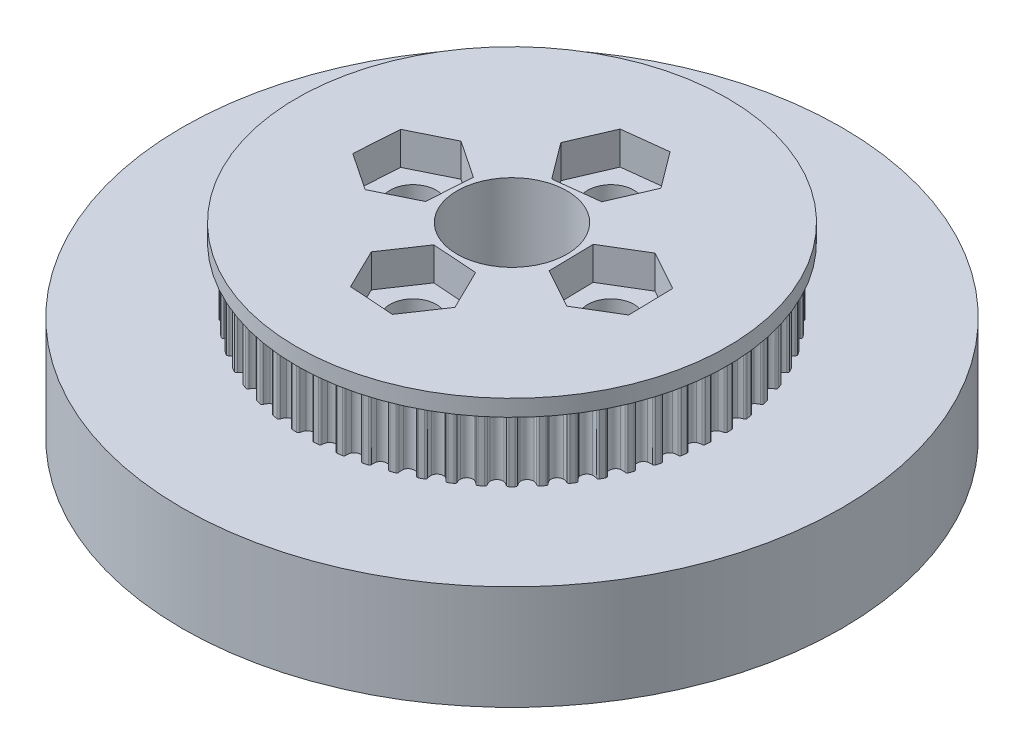
SolidWorks part; units mm, degrees
ref_plane "Front Plane" through (0, 0, 0) normal (0, 0, 1) x (1, 0, 0)
ref_plane "Top Plane" through (0, 0, 0) normal (0, 1, 0) x (1, 0, 0)
ref_plane "Right Plane" through (0, 0, 0) normal (1, 0, 0) x (0, 0, -1)
sketch "Sketch1" plane through (0, 0, 0) normal (0, 1, 0) x (1, 0, 0)
  circle A0 centre (0, 0) radius 18.8446
  dimension "D1" = 37.6892
extrude "Boss-Extrude1" add sketch "Sketch1" along normal blind 6
sketch "Sketch2" plane through (0, 6, 0) normal (0, 1, 0) x (1, 0, 0)
  line L0 (0, 0) -> (0, 18.8446) construction
  line L1 (0, 18.8446) -> (-0.4, 18.8446) construction
  line L2 (0, 18.8446) -> (0.4, 18.8446) construction
  circle A0 centre (0, 0) radius 18.8446
  circle A1 centre (0, 0) radius 18.6396 construction
  circle A2 centre (0, 0) radius 18.0846 construction
  arc A4 (-0.6199, 18.8344) -> (-0.4536, 18.2862) centre (0.4, 18.8446) ccw
  arc A5 (-0.4536, 18.2862) -> (0.4536, 18.2862) centre (0, 18.6396) ccw
  arc A6 (0.4536, 18.2862) -> (0.6199, 18.8344) centre (-0.4, 18.8446) ccw
  dimension "D1" = 37.6892
  dimension "D2" = 36.1692
  dimension "D3" = 37.2792
  dimension "D7" = 2.04
  dimension "D8" = 1.15
  dimension "D4" = 0.4
  dimension "D5" = 0.4
extrude "Cut-Extrude1" cut sketch "Sketch2" against normal blind 10 contours A5 A6 A0 A4 region at (0, 6, -18.5075)
fillet "Fillet1" radius 0.17 2 edges at (0.6199, 3, -18.8344) (-0.6199, 3, -18.8344)
ref_axis "Axis2" through (0, 6, 0) along (0, -1, 0)
pattern_circular "CirPattern2" count 60 over 360 about axis through (0, 6, 0) along (0, -1, 0) of "Cut-Extrude1", "Fillet1"
sketch "Sketch3" plane through (0, 6, 0) normal (0, 1, 0) x (1, 0, 0)
  circle A0 centre (0, 0) radius 19.5946
  dimension "D1" = 39.1892
extrude "Boss-Extrude2" add sketch "Sketch3" along normal blind 1.5
sketch "Sketch4" plane through (0, 0, 0) normal (0, -1, 0) x (1, 0, 0)
  circle A0 centre (0, 0) radius 30
  dimension "D1" = 60
extrude "Boss-Extrude3" add sketch "Sketch4" along normal blind 9.5
sketch "Sketch5" plane through (0, -9.5, 0) normal (0, -1, 0) x (1, 0, 0)
  circle A0 centre (0, 0) radius 24.5
  dimension "D1" = 49
extrude "Cut-Extrude2" cut sketch "Sketch5" against normal blind 4
sketch "Sketch6" plane through (0, -5.5, 0) normal (0, -1, 0) x (1, 0, 0)
  circle A0 centre (0, 0) radius 17
  dimension "D1" = 34
extrude "Boss-Extrude4" add sketch "Sketch6" along normal blind 2
sketch "Sketch7" plane through (0, -7.5, 0) normal (0, -1, 0) x (1, 0, 0)
  circle A0 centre (0, 0) radius 12.25
  dimension "D1" = 24.5
extrude "Boss-Extrude5" add sketch "Sketch7" along normal blind 13
sketch "Sketch8" plane through (0, -20.5, 0) normal (0, -1, 0) x (1, 0, 0)
  circle A0 centre (0, 0) radius 9 construction
  circle A1 centre (0, 9) radius 2.1
  circle A2 centre (9, 0) radius 2.1
  circle A3 centre (0, -9) radius 2.1
  circle A4 centre (-9, 0) radius 2.1
  dimension "D1" = 4.2
  dimension "D2" = 18
extrude "Cut-Extrude3" cut sketch "Sketch8" against normal through all
sketch "Sketch9" plane through (0, 7.5, 0) normal (0, 1, 0) x (1, 0, 0)
  line L31 (5.4102, 1.979) -> (5.4912, -2.1194)
  line L32 (5.4912, -2.1194) -> (9.0811, -4.0984)
  line L33 (9.0811, -4.0984) -> (12.5898, -1.979)
  line L34 (12.5898, -1.979) -> (12.5088, 2.1194)
  line L35 (12.5088, 2.1194) -> (8.9189, 4.0984)
  line L36 (8.9189, 4.0984) -> (5.4102, 1.979)
  line L37 (-4.0711, 8.5212) -> (-1.6209, 5.2349)
  line L38 (-1.6209, 5.2349) -> (2.4502, 5.7137)
  line L39 (2.4502, 5.7137) -> (4.0711, 9.4788)
  line L40 (4.0711, 9.4788) -> (1.6209, 12.7651)
  line L41 (1.6209, 12.7651) -> (-2.4502, 12.2863)
  line L42 (-2.4502, 12.2863) -> (-4.0711, 8.5212)
  line L43 (-5.3231, 1.8122) -> (-8.731, 4.0903)
  line L44 (-8.731, 4.0903) -> (-12.4078, 2.2782)
  line L45 (-12.4078, 2.2782) -> (-12.6769, -1.8122)
  line L46 (-12.6769, -1.8122) -> (-9.269, -4.0903)
  line L47 (-9.269, -4.0903) -> (-5.5922, -2.2782)
  line L48 (-5.5922, -2.2782) -> (-5.3231, 1.8122)
  line L49 (-1.7979, -5.3161) -> (-4.0893, -8.7151)
  line L50 (-4.0893, -8.7151) -> (-2.2914, -12.399)
  line L51 (-2.2914, -12.399) -> (1.7979, -12.6839)
  line L52 (1.7979, -12.6839) -> (4.0893, -9.2849)
  line L53 (4.0893, -9.2849) -> (2.2914, -5.601)
  line L54 (2.2914, -5.601) -> (-1.7979, -5.3161)
  circle A0 centre (9, 0) radius 3.55 construction
  circle A1 centre (0, 9) radius 3.55 construction
  circle A2 centre (-9, 0) radius 3.55 construction
  circle A3 centre (0, -9) radius 3.55 construction
  dimension "D1" = 7.1
  dimension "D2" = 7.1
  dimension "D3" = 7.1
  dimension "D4" = 7.1
extrude "Cut-Extrude4" cut sketch "Sketch9" against normal blind 3
sketch "Sketch10" plane through (0, 7.5, 0) normal (0, 1, 0) x (1, 0, 0)
  circle A0 centre (0, 0) radius 5
  dimension "D1" = 10
extrude "Cut-Extrude5" cut sketch "Sketch10" against normal up to next
equation "\"GD\"= 0.76mm"
equation "\"SBD\"= 2mm"
equation "\"NT\"= 60"
equation "\"PD\"= ( \"SBD\" * \"NT\" ) / 3.14159"
equation "\"U\"= 0.254mm"
equation "\"OD\"= \"PD\" - ( 2 * \"U\" )"
equation "\"RD\"= \"OD\" - ( 2 * \"GD\" )"
equation "\"R3\"= 0.555mm"
equation "\"R2\"= 1mm"
equation "\"R1\"= 0.15mm"
equation "\"DT\"= 0.02mm"
equation "\"b\"= 0.4mm"
equation "\"D1@Sketch1\"= \"OD\""
equation "\"D1@Sketch2\"= \"OD\""
equation "\"D3@Sketch2\"= \"RD\" + \"R3\" * 2"
equation "\"D2@Sketch2\"= \"RD\""
equation "\"D4@Sketch2\"= \"b\""
equation "\"D5@Sketch2\"= \"b\""
equation "\"D7@Sketch2\"= ( \"R2\" + \"DT\" ) * 2"
equation "\"D8@Sketch2\"= ( \"R3\" + \"DT\" ) * 2"
equation "\"D1@Fillet1\"=\"R1\"+\"DT\""
equation "\"D1@CirPattern2\"=\"NT\""
equation "\"D1@Sketch3\"=\"OD\"+1.5mm"
